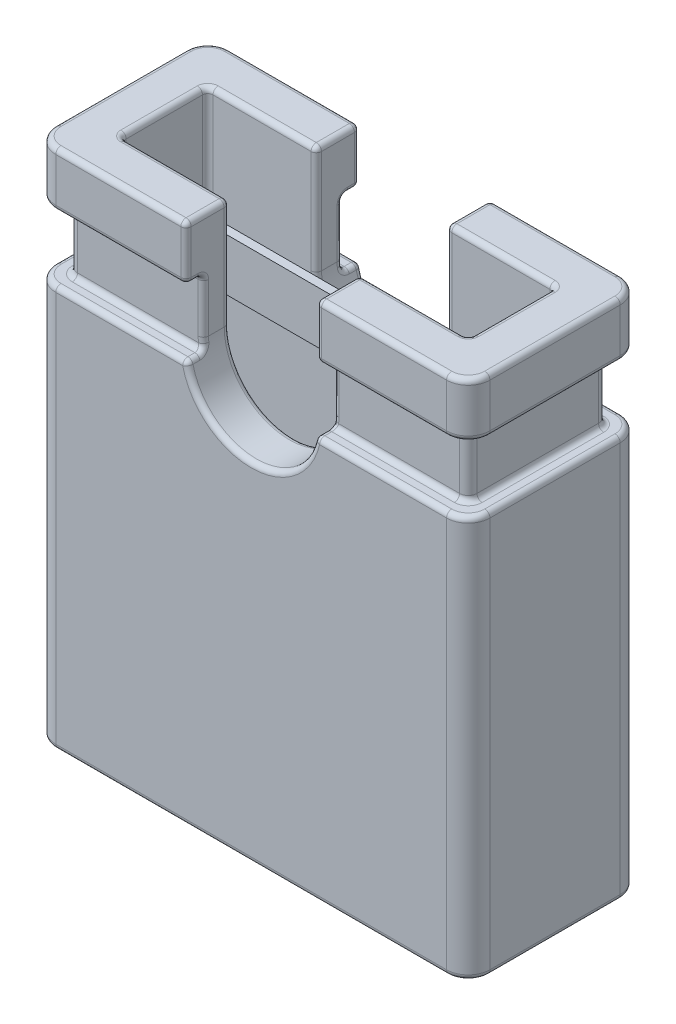
SolidWorks part; units mm, degrees
ref_plane "Front Plane" through (0, 0, 0) normal (0, 0, 1) x (1, 0, 0)
ref_plane "Top Plane" through (0, 0, 0) normal (0, 1, 0) x (1, 0, 0)
ref_plane "Right Plane" through (0, 0, 0) normal (1, 0, 0) x (0, 0, -1)
ref_plane "Plane1" through (0, 0, 0) normal (0, 0, 1) x (1, 0, 0)
sketch "Sketch1" plane through (0, 0, 0) normal (0, 0, 1) x (1, 0, 0)
  line L0 (-2.5, 7) -> (-0.75, 7)
  line L1 (0.75, 7) -> (2.5, 7)
  line L2 (2.5, 7) -> (2.5, 1)
  line L3 (2.5, 1) -> (-2.5, 1)
  line L4 (-2.5, 1) -> (-2.5, 7)
  line L5 (0.75, 5.75) -> (0.75, 7)
  line L6 (-0.75, 5.75) -> (-0.75, 7)
  arc A0 (-0.75, 5.75) -> (0.75, 5.75) centre (0, 5.75) ccw
extrude "Boss-Extrude1" add sketch "Sketch1" along normal blind 1 and the other way blind 1
ref_plane "Plane2" through (0, 0, 0) normal (0, -1, 0) x (1, 0, 0)
sketch "Sketch2" plane through (0, 0, 0) normal (0, -1, 0) x (1, 0, 0)
  line L0 (-2, 0.5) -> (2, 0.5)
  line L1 (2, 0.5) -> (2, -0.5)
  line L2 (2, -0.5) -> (-2, -0.5)
  line L3 (-2, -0.5) -> (-2, 0.5)
extrude "Cut-Extrude1" cut sketch "Sketch2" against normal through all
ref_plane "Plane3" through (0, 6, -1) normal (0, 1, 0) x (0, 0, -1)
sketch "Sketch3" plane through (0, 6, -1) normal (0, 1, 0) x (0, 0, -1)
  line L0 (-1.7, 2.3) -> (-0.3, 2.3)
  line L1 (-0.2, 2.2) -> (-0.2, -2.2)
  line L2 (-0.3, -2.3) -> (-1.7, -2.3)
  line L3 (-1.8, -2.2) -> (-1.8, 2.2)
  arc A0 (-0.2, 2.2) -> (-0.3, 2.3) centre (-0.3, 2.2) ccw
  arc A1 (-1.7, 2.3) -> (-1.8, 2.2) centre (-1.7, 2.2) ccw
  arc A2 (-1.8, -2.2) -> (-1.7, -2.3) centre (-1.7, -2.2) ccw
  arc A3 (-0.3, -2.3) -> (-0.2, -2.2) centre (-0.3, -2.2) ccw
extrude "Cut-Extrude2" cut sketch "Sketch3" against normal blind 0.375 and the other way blind 0.375 flip side to cut
fillet "Fillet1" radius 0.25 8 edges at (-2.5, 6.6875, -1) (-2.5, 3.3125, -1) (-2.5, 3.3125, 1) (-2.5, 6.6875, 1) (2.5, 6.6875, -1) (2.5, 3.3125, -1) (2.5, 3.3125, 1) (2.5, 6.6875, 1)
fillet "Fillet2" radius 0.06 54 edges at (1.475, 6.375, -0.8) (2.2707, 6.375, -0.7707) (2.3, 6.375, 0) (2.2707, 6.375, 0.7707) (1.475, 6.375, 0.8) (-1.5, 6.375, -1) (-2.4268, 6.375, -0.9268) (-2.5, 6.375, 0) (-2.4268, 6.375, 0.9268) (-1.5, 6.375, 1) (-1.4948, 5.625, -1) (-2.4268, 5.625, -0.9268) (-2.5, 5.625, 0) (-2.4268, 5.625, 0.9268) (-1.4948, 5.625, 1) (1.4948, 5.625, -1) (2.4268, 5.625, -0.9268) (2.5, 5.625, 0) (2.4268, 5.625, 0.9268) (1.4948, 5.625, 1) (2, 4, 0.5) (2, 4, -0.5) (-2, 4, 0.5) (-2, 4, -0.5) (1.5, 7, 1) (2.4268, 7, 0.9268) (2.5, 7, 0) (2.4268, 7, -0.9268) (1.5, 7, -1) (-1.5, 7, -1) (-2.4268, 7, -0.9268) (-2.5, 7, 0) (-2.4268, 7, 0.9268) (-1.5, 7, 1) (1.5, 6.375, -1) (2.4268, 6.375, -0.9268) (2.5, 6.375, 0) (2.4268, 6.375, 0.9268) (1.5, 6.375, 1) (-1.475, 6.375, -0.8) (-2.2707, 6.375, -0.7707) (-2.3, 6.375, 0) (-2.2707, 6.375, 0.7707) (-1.475, 6.375, 0.8) (-1.4698, 5.625, -0.8) (-2.2707, 5.625, -0.7707) (-2.3, 5.625, 0) (-2.2707, 5.625, 0.7707) (-1.4698, 5.625, 0.8) (1.4698, 5.625, -0.8) (2.2707, 5.625, -0.7707) (2.3, 5.625, 0) (2.2707, 5.625, 0.7707) (1.4698, 5.625, 0.8)
fillet "Fillet3" radius 0.06 10 edges at (1.345, 7, 0.5) (1.9824, 7, 0.4824) (2, 7, 0) (1.9824, 7, -0.4824) (1.345, 7, -0.5) (-1.345, 7, 0.5) (-1.9824, 7, 0.4824) (-2, 7, 0) (-1.9824, 7, -0.4824) (-1.345, 7, -0.5)
fillet "Fillet4" radius 0.06 64 edges at (2.5, 1, 0) (2.4268, 1, -0.9268) (0, 1, -1) (-2.4268, 1, -0.9268) (-2.5, 1, 0) (-2.4268, 1, 0.9268) (0, 1, 1) (2.4268, 1, 0.9268) (0, 5, -0.5) (0.75, 6.345, -0.5) (0.75, 6.9824, -0.5176) (0.75, 7, -0.75) (0.75, 6.9824, -0.9824) (0.75, 6.6875, -1) (0.75, 6.3926, -0.9824) (0.75, 6.375, -0.9) (0.75, 6.3574, -0.8176) (0.75, 6.0325, -0.8) (0.7493, 5.7175, -0.8) (0.7429, 5.6474, -0.8132) (0.7395, 5.625, -0.9) (0.7372, 5.6122, -0.977) (0, 5, -1) (-0.7355, 5.6031, -0.9864) (-0.7395, 5.625, -0.9) (-0.7416, 5.6379, -0.8229) (-0.7493, 5.7175, -0.8) (-0.75, 6.0325, -0.8) (-0.75, 6.3574, -0.8176) (-0.75, 6.375, -0.9) (-0.75, 6.3926, -0.9824) (-0.75, 6.6875, -1) (-0.75, 6.9824, -0.9824) (-0.75, 7, -0.75) (-0.75, 6.9824, -0.5176) (-0.75, 6.345, -0.5) (0.7355, 5.6031, 0.9864) (0.7395, 5.625, 0.9) (0.7416, 5.6379, 0.8229) (0.7493, 5.7175, 0.8) (0.75, 6.0325, 0.8) (0.75, 6.3574, 0.8176) (0.75, 6.375, 0.9) (0.75, 6.3926, 0.9824) (0.75, 6.6875, 1) (0.75, 6.9824, 0.9824) (0.75, 7, 0.75) (0.75, 6.9824, 0.5176) (0.75, 6.345, 0.5) (0, 5, 0.5) (-0.75, 6.345, 0.5) (-0.75, 6.9824, 0.5176) (-0.75, 7, 0.75) (-0.75, 6.9824, 0.9824) (-0.75, 6.6875, 1) (-0.75, 6.3926, 0.9824) (-0.75, 6.375, 0.9) (-0.75, 6.3574, 0.8176) (-0.75, 6.0325, 0.8) (-0.7493, 5.7175, 0.8) (-0.7429, 5.6474, 0.8132) (-0.7395, 5.625, 0.9) (-0.7372, 5.6122, 0.977) (0, 5, 1)
ref_plane "Plane4" through (0, 0, 0) normal (1, 0, 0) x (0, 1, 0)
sketch "Sketch4" plane through (0, 0, 0) normal (1, 0, 0) x (0, 1, 0)
  line L0 (6, 0.475) -> (6.6, 0.475)
  line L1 (6.6, 0.475) -> (6.6, 0.375)
  line L2 (6.6, 0.375) -> (6, 0.375)
  line L3 (6, 0.375) -> (6, 0.475)
extrude "Boss-Extrude2" add sketch "Sketch4" along normal blind 2 and the other way blind 2
